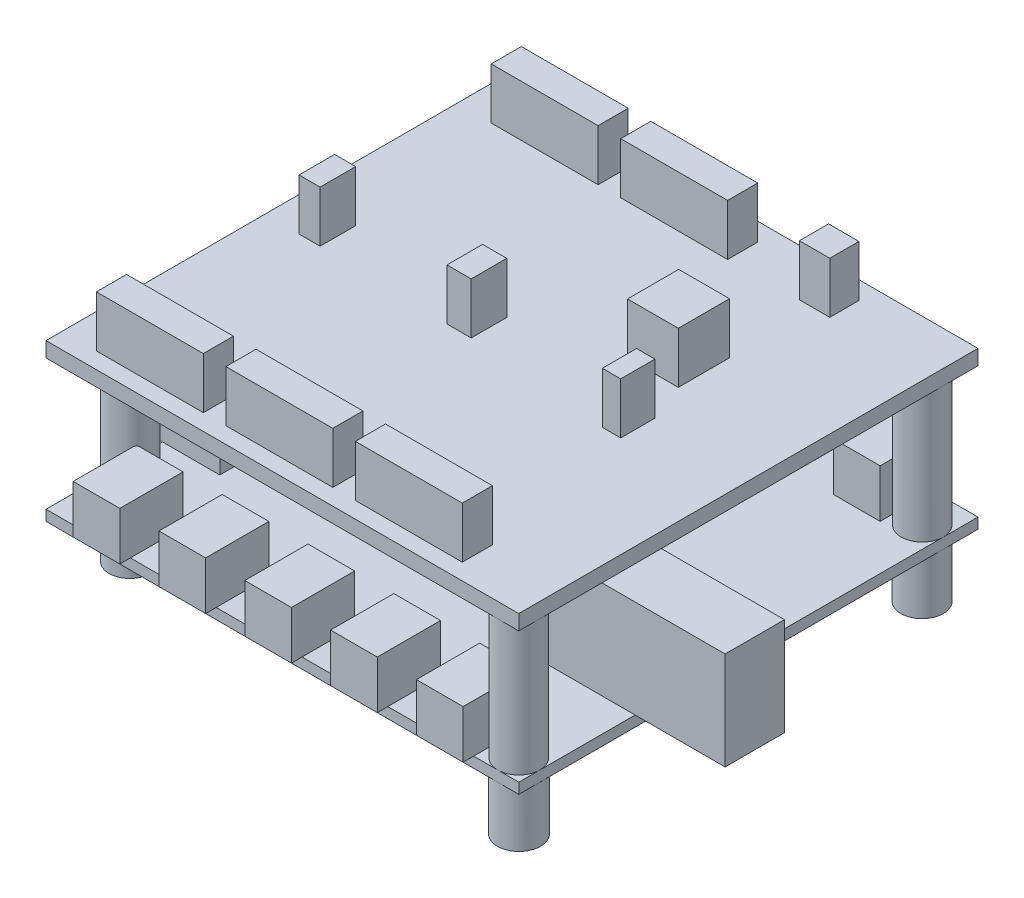
SolidWorks part; units mm, degrees
ref_plane "Front Plane" through (0, 0, 0) normal (0, 0, 1) x (1, 0, 0)
ref_plane "Top Plane" through (0, 0, 0) normal (0, 1, 0) x (1, 0, 0)
ref_plane "Right Plane" through (0, 0, 0) normal (1, 0, 0) x (0, 0, -1)
sketch "Sketch1" plane through (0, 0, 0) normal (0, 1, 0) x (1, 0, 0)
  line L1 (-39.878, -38.735) -> (39.878, -38.735)
  line L2 (-39.878, -38.735) -> (-39.878, 38.735)
  line L3 (-39.878, 38.735) -> (39.878, 38.735)
  line L4 (39.878, -38.735) -> (39.878, 38.735)
  line L5 (-39.878, -38.735) -> (39.878, 38.735) construction
  line L6 (-39.878, 38.735) -> (39.878, -38.735) construction
  point P0 (0, 0)
  dimension "D1" = 79.756
  dimension "D2" = 77.47
extrude "Boss-Extrude1" add sketch "Sketch1" along normal blind 2.54
sketch "Sketch5" plane through (0, 0, 0) normal (0, -1, 0) x (1, 0, 0)
  line L0 (39.878, 35.179) -> (36.322, 35.179) construction
  line L1 (39.878, 38.735) -> (39.878, -38.735) construction
  line L2 (36.322, 35.179) -> (36.322, 38.735) construction
  line L3 (-39.878, 38.735) -> (39.878, 38.735) construction
  circle A0 centre (36.322, 35.179) radius 3.556
  dimension "D1" = 3.556
extrude "Boss-Extrude2" add sketch "Sketch5" along normal blind 22.098
sketch "Sketch6" plane through (0, 0, 0) normal (0, -1, 0) x (1, 0, 0)
  line L0 (39.878, -38.735) -> (39.878, -32.893) construction
  line L1 (39.878, 35.179) -> (39.878, -38.735) construction
  line L2 (39.878, -32.893) -> (36.322, -32.893)
  circle A0 centre (36.322, -32.893) radius 3.556
  dimension "D1" = 3.556
extrude "Boss-Extrude3" add sketch "Sketch6" along normal blind 22.098 contours A0 region at (32.8666, 0, -32.893)
sketch "Sketch7" plane through (0, 0, 0) normal (0, -1, 0) x (1, 0, 0)
  line L0 (-39.878, 38.735) -> (-39.878, 28.067)
  line L1 (-39.878, -38.735) -> (-39.878, 38.735) construction
  line L2 (-39.878, 28.067) -> (-36.322, 28.067)
  circle A0 centre (-36.322, 28.067) radius 3.556
  dimension "D1" = 3.556
extrude "Boss-Extrude4" add sketch "Sketch7" along normal blind 22.098 contours A0
sketch "Sketch8" plane through (0, 0, 0) normal (0, -1, 0) x (1, 0, 0)
  line L0 (-39.878, -38.735) -> (-39.878, -28.067) construction
  line L1 (-39.878, -38.735) -> (-39.878, 28.067) construction
  line L2 (-39.878, -28.067) -> (-36.322, -28.067) construction
  circle A0 centre (-36.322, -28.067) radius 3.556
extrude "Boss-Extrude5" add sketch "Sketch8" along normal blind 22.098
sketch "Sketch9" plane through (0, -22.098, 0) normal (0, -1, 0) x (1, 0, 0)
  line L0 (36.322, 35.179) -> (39.878, 35.179) construction
  line L1 (36.322, 35.179) -> (36.322, 38.735) construction
  line L2 (36.322, 38.735) -> (39.8849, 38.735) construction
  line L8 (39.8849, 38.735) -> (-39.8711, 38.735)
  line L9 (39.8849, 38.735) -> (39.8849, -38.735)
  line L10 (39.8849, -38.735) -> (-39.8711, -38.735)
  line L11 (-39.8711, 38.735) -> (-39.8711, -38.735)
  circle A0 centre (36.322, 35.179) radius 3.556 construction
  dimension "D1" = 79.756
  dimension "D2" = 77.47
extrude "Boss-Extrude6" add sketch "Sketch9" along normal blind 1.778
ref_point "Point1"
ref_axis "Axis1" through (-36.322, -22.098, -28.067) along (0, -1, 0)
ref_point "Point2"
ref_point "Point3"
ref_point "Point4"
ref_axis "Axis2" through (36.322, -22.098, -32.893) along (0, -1, 0)
ref_axis "Axis3" through (36.322, -22.098, 35.179) along (0, -1, 0)
ref_axis "Axis4" through (-36.322, -22.098, 28.067) along (0, -1, 0)
sketch "Sketch13" plane through (0, -23.876, 0) normal (0, -1, 0) x (1, 0, 0)
  circle A0 centre (-36.2987, -28.0576) radius 3.5725
extrude "Boss-Extrude8" add sketch "Sketch13" along normal blind 9.398
sketch "Sketch14" plane through (0, -23.876, 0) normal (0, -1, 0) x (-1, 0, 0)
  circle A0 centre (-36.3031, 32.8842) radius 3.5818
extrude "Boss-Extrude9" add sketch "Sketch14" along normal blind 9.398
sketch "Sketch15" plane through (0, -23.876, 0) normal (0, -1, 0) x (1, 0, 0)
  circle A0 centre (-36.3393, 28.0982) radius 3.5319
extrude "Boss-Extrude10" add sketch "Sketch15" along normal blind 9.398
sketch "Sketch16" plane through (0, -23.876, 0) normal (0, -1, 0) x (1, 0, 0)
  circle A0 centre (36.2797, 35.096) radius 3.639
extrude "Boss-Extrude11" add sketch "Sketch16" along normal blind 9.398
sketch "Sketch17" plane through (0, 2.54, 0) normal (0, 1, 0) x (1, 0, 0)
  line L0 (-12.2641, 30.607) -> (-16.0741, 30.607) construction
  line L1 (-34.1081, 30.607) -> (-16.0741, 30.607)
  line L2 (-34.1081, 30.607) -> (-34.1081, 35.687)
  line L3 (-34.1081, 35.687) -> (-16.0741, 35.687)
  line L4 (-16.0741, 30.607) -> (-16.0741, 35.687)
  line L5 (-12.2641, 30.607) -> (5.7699, 30.607)
  line L6 (-12.2641, 30.607) -> (-12.2641, 35.687)
  line L7 (-12.2641, 35.687) -> (5.7699, 35.687)
  line L8 (5.7699, 30.607) -> (5.7699, 35.687)
  line L9 (39.878, 38.735) -> (-39.878, 38.735) construction
  line L10 (-34.1081, 35.687) -> (-34.1081, 38.735) construction
  line L11 (9.5799, -35.9948) -> (5.7699, -35.9948) construction
  line L12 (-34.1081, -30.9148) -> (-16.0741, -30.9148)
  line L13 (-34.1081, -30.9148) -> (-34.1081, -35.9948)
  line L14 (-34.1081, -35.9948) -> (-16.0741, -35.9948)
  line L15 (-16.0741, -30.9148) -> (-16.0741, -35.9948)
  line L16 (-12.2641, -35.9948) -> (5.7699, -35.9948)
  line L17 (-12.2641, -35.9948) -> (-12.2641, -30.9148)
  line L18 (-12.2641, -30.9148) -> (5.7699, -30.9148)
  line L19 (5.7699, -35.9948) -> (5.7699, -30.9148)
  line L20 (9.5799, -35.9948) -> (27.6139, -35.9948)
  line L21 (9.5799, -35.9948) -> (9.5799, -30.9148)
  line L22 (9.5799, -30.9148) -> (27.6139, -30.9148)
  line L23 (27.6139, -35.9948) -> (27.6139, -30.9148)
  line L24 (-12.2641, -35.9948) -> (-16.0741, -35.9948) construction
  line L26 (11.7252, 16.403) -> (20.294, 16.403)
  line L27 (11.7252, 16.403) -> (11.7252, 7.7644)
  line L28 (11.7252, 7.7644) -> (20.294, 7.7644)
  line L29 (20.294, 16.403) -> (20.294, 7.7644)
  line L30 (22.8449, 30.7744) -> (17.7167, 30.7744)
  line L31 (22.8449, 30.7744) -> (22.8449, 35.687)
  line L32 (22.8449, 35.687) -> (17.7167, 35.687)
  line L33 (17.7167, 30.7744) -> (17.7167, 35.687)
  line L34 (22.8264, -4.483) -> (19.7275, -4.483)
  line L35 (22.8264, -4.483) -> (22.8264, 1.2833)
  line L36 (22.8264, 1.2833) -> (19.7275, 1.2833)
  line L37 (19.7275, -4.483) -> (19.7275, 1.2833)
  line L38 (-4.3947, -2.4898) -> (-8.4737, -2.4898)
  line L39 (-4.3947, -2.4898) -> (-4.3947, 3.5141)
  line L40 (-4.3947, 3.5141) -> (-8.4737, 3.5141)
  line L41 (-8.4737, -2.4898) -> (-8.4737, 3.5141)
  line L42 (-30.5466, -1.8269) -> (-34.096, -1.8269)
  line L43 (-30.5466, -1.8269) -> (-30.5466, 4.1771)
  line L44 (-30.5466, 4.1771) -> (-34.096, 4.1771)
  line L45 (-34.096, -1.8269) -> (-34.096, 4.1771)
  dimension "D1" = 18.034
  dimension "D2" = 5.08
  dimension "D3" = 3.048
extrude "Boss-Extrude12" add sketch "Sketch17" along normal blind 8.636
sketch "Sketch18" plane through (0, -22.098, 0) normal (0, 1, 0) x (1, 0, 0)
  line L0 (-39.8711, 38.735) -> (39.8849, 38.735) construction
  line L1 (32.2649, 38.735) -> (24.3909, 38.735) construction
  line L2 (32.2649, 38.735) -> (32.2649, 29.845)
  line L3 (32.2649, 29.845) -> (24.3909, 29.845)
  line L4 (24.3909, 38.735) -> (24.3909, 29.845)
  line L5 (24.3909, 38.735) -> (17.7869, 38.735) construction
  line L6 (17.7869, 38.735) -> (9.9129, 38.735) construction
  line L7 (17.7869, 38.735) -> (17.7869, 29.845)
  line L8 (17.7869, 29.845) -> (9.9129, 29.845)
  line L9 (9.9129, 38.735) -> (9.9129, 29.845)
  line L10 (3.3089, 38.735) -> (-4.5651, 38.735) construction
  line L11 (3.3089, 38.735) -> (3.3089, 29.845)
  line L12 (3.3089, 29.845) -> (-4.5651, 29.845)
  line L13 (-4.5651, 38.735) -> (-4.5651, 29.845)
  line L14 (-11.1691, 38.735) -> (-19.0431, 38.735) construction
  line L15 (-11.1691, 38.735) -> (-11.1691, 29.845)
  line L16 (-11.1691, 29.845) -> (-19.0431, 29.845)
  line L17 (-19.0431, 38.735) -> (-19.0431, 29.845)
  line L18 (-25.6471, 38.735) -> (-33.5211, 38.735) construction
  line L19 (-25.6471, 38.735) -> (-25.6471, 29.845)
  line L20 (-25.6471, 29.845) -> (-33.5211, 29.845)
  line L21 (-33.5211, 38.735) -> (-33.5211, 29.845)
  line L22 (9.9129, 38.735) -> (3.3089, 38.735) construction
  line L23 (-4.5651, 38.735) -> (-11.1691, 38.735) construction
  line L24 (-19.0431, 38.735) -> (-25.6471, 38.735) construction
  line L25 (32.2649, 34.29) -> (39.8849, 34.29) construction
  line L26 (39.8849, 38.735) -> (39.8849, -38.735) construction
  line L28 (-25.6471, 38.735) -> (-33.5211, 38.735) construction
  line L29 (-25.6471, 38.735) -> (-25.6471, 40.513)
  line L30 (-25.6471, 40.513) -> (-33.5211, 40.513)
  line L31 (-33.5211, 38.735) -> (-33.5211, 40.513)
  line L32 (-11.1691, 38.735) -> (-19.0431, 38.735) construction
  line L33 (-11.1691, 38.735) -> (-11.1691, 40.513)
  line L34 (-11.1691, 40.513) -> (-19.0431, 40.513)
  line L35 (-19.0431, 38.735) -> (-19.0431, 40.513)
  line L36 (-4.5651, 38.735) -> (3.3089, 38.735) construction
  line L37 (-4.5651, 38.735) -> (-4.5651, 40.513)
  line L38 (-4.5651, 40.513) -> (3.3089, 40.513)
  line L39 (3.3089, 38.735) -> (3.3089, 40.513)
  line L40 (9.9129, 38.735) -> (17.7869, 38.735) construction
  line L41 (9.9129, 38.735) -> (9.9129, 40.513)
  line L42 (9.9129, 40.513) -> (17.7869, 40.513)
  line L43 (17.7869, 38.735) -> (17.7869, 40.513)
  line L44 (24.3909, 38.735) -> (32.2649, 38.735) construction
  line L45 (24.3909, 38.735) -> (24.3909, 40.513)
  line L46 (24.3909, 40.513) -> (32.2649, 40.513)
  line L47 (32.2649, 38.735) -> (32.2649, 40.513)
  dimension "D1" = 8.89
  dimension "D2" = 7.874
  dimension "D3" = 6.604
  dimension "D4" = 7.62
  dimension "D5" = 1.778
extrude "Boss-Extrude13" add sketch "Sketch18" along normal blind 8.128
mirror "Mirror1" about plane through (0, 0, 0) normal (0, 0, 1) of "Boss-Extrude13"
sketch "Sketch19" plane through (0, -22.098, 0) normal (0, 1, 0) x (1, 0, 0)
  line L0 (-39.8711, 22.6901) -> (-39.8711, 15.0701) construction
  line L1 (-30.2191, 22.6901) -> (-41.6491, 22.6901)
  line L2 (-30.2191, 22.6901) -> (-30.2191, 15.0701)
  line L3 (-30.2191, 15.0701) -> (-41.6491, 15.0701)
  line L4 (-41.6491, 22.6901) -> (-41.6491, 15.0701)
  line L5 (-30.2191, 6.8181) -> (-41.6491, 6.8181)
  line L6 (-30.2191, 6.8181) -> (-30.2191, -0.8019)
  line L7 (-30.2191, -0.8019) -> (-41.6491, -0.8019)
  line L8 (-41.6491, 6.8181) -> (-41.6491, -0.8019)
  line L9 (-30.2191, -11.4556) -> (-41.6491, -11.4556)
  line L10 (-30.2191, -11.4556) -> (-30.2191, -19.0756)
  line L11 (-30.2191, -19.0756) -> (-41.6491, -19.0756)
  line L12 (-41.6491, -11.4556) -> (-41.6491, -19.0756)
  line L13 (-39.8711, -27.846) -> (-39.8711, 27.846) construction
  line L14 (-39.8711, 15.0701) -> (-41.6491, 15.0701) construction
  dimension "D1" = 1.778
  dimension "D2" = 11.43
  dimension "D3" = 7.62
extrude "Boss-Extrude14" add sketch "Sketch19" along normal blind 8.128
sketch "Sketch20" plane through (0, -22.098, 0) normal (0, 1, 0) x (1, 0, 0)
  line L1 (24.6819, -19.1084) -> (55.0661, -19.1084)
  line L2 (24.6819, -19.1084) -> (24.6819, -9.0937)
  line L3 (24.6819, -9.0937) -> (55.0661, -9.0937)
  line L4 (55.0661, -19.1084) -> (55.0661, -9.0937)
extrude "Boss-Extrude15" add sketch "Sketch20" along normal blind 16.51
